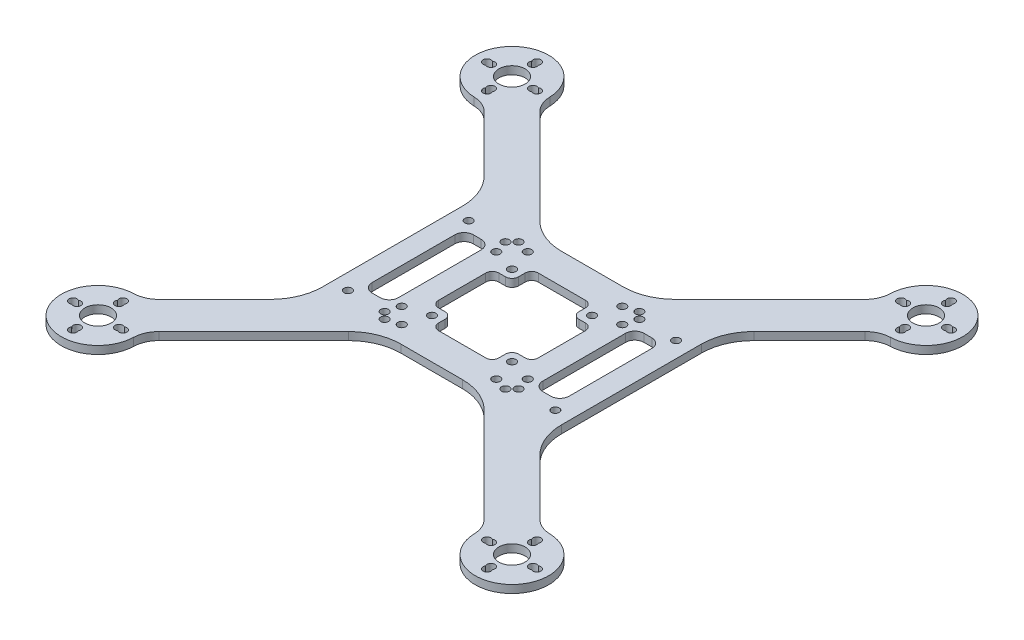
SolidWorks part; units mm, degrees
material "碳纤维板"
ref_plane "前视基准面" through (0, 0, 0) normal (0, 0, 1) x (1, 0, 0)
ref_plane "上视基准面" through (0, 0, 0) normal (0, 1, 0) x (1, 0, 0)
ref_plane "右视基准面" through (0, 0, 0) normal (1, 0, 0) x (0, 0, -1)
sketch "草图1" plane through (0, 0, 0) normal (0, 1, 0) x (1, 0, 0)
  line L1 (-42.5, 30.6) -> (42.5, 30.6)
  line L2 (-45.5, 27.6) -> (-45.5, -27.6)
  line L3 (-42.5, -30.6) -> (42.5, -30.6)
  line L4 (45.5, 27.6) -> (45.5, -27.6)
  line L5 (-45.5, 30.6) -> (45.5, -30.6) construction
  line L6 (-45.5, -30.6) -> (45.5, 30.6) construction
  line L7 (-25.5, 23) -> (25.5, 23) construction
  line L8 (-25.5, 23) -> (-25.5, -23) construction
  line L9 (-25.5, -23) -> (25.5, -23) construction
  line L10 (25.5, 23) -> (25.5, -23) construction
  line L11 (-25.5, 23) -> (25.5, -23) construction
  line L12 (-25.5, -23) -> (25.5, 23) construction
  line L13 (-39.5, -23) -> (39.5, -23) construction
  line L14 (-39.5, -23) -> (-39.5, 23) construction
  line L15 (-39.5, 23) -> (39.5, 23) construction
  line L16 (39.5, -23) -> (39.5, 23) construction
  line L17 (-39.5, -23) -> (39.5, 23) construction
  line L18 (-39.5, 23) -> (39.5, -23) construction
  line L19 (-24, -18) -> (24, -18) construction
  line L20 (-24, -18) -> (-24, 18) construction
  line L21 (-24, 18) -> (24, 18) construction
  line L22 (24, -18) -> (24, 18) construction
  line L23 (-24, -18) -> (24, 18) construction
  line L24 (-24, 18) -> (24, -18) construction
  line L25 (-18, -24) -> (18, -24) construction
  line L26 (-18, -24) -> (-18, 24) construction
  line L27 (-18, 24) -> (18, 24) construction
  line L28 (18, -24) -> (18, 24) construction
  line L29 (-18, -24) -> (18, 24) construction
  line L30 (-18, 24) -> (18, -24) construction
  line L31 (-23, -25.5) -> (23, -25.5) construction
  line L32 (-23, -25.5) -> (-23, 25.5) construction
  line L33 (-23, 25.5) -> (23, 25.5) construction
  line L34 (23, -25.5) -> (23, 25.5) construction
  line L35 (-23, -25.5) -> (23, 25.5) construction
  line L36 (-23, 25.5) -> (23, -25.5) construction
  circle A0 centre (-39.5, 23) radius 1.5
  circle A1 centre (-25.5, 23) radius 1.5
  circle A2 centre (25.5, 23) radius 1.5
  circle A3 centre (39.5, 23) radius 1.5
  circle A4 centre (-39.5, -23) radius 1.5
  circle A5 centre (-25.5, -23) radius 1.5
  circle A6 centre (25.5, -23) radius 1.5
  circle A7 centre (39.5, -23) radius 1.5
  arc A8 (-45.5, -27.6) -> (-42.5, -30.6) centre (-42.5, -27.6) ccw
  arc A9 (42.5, -30.6) -> (45.5, -27.6) centre (42.5, -27.6) ccw
  arc A10 (42.5, 30.6) -> (45.5, 27.6) centre (42.5, 27.6) cw
  arc A11 (-42.5, 30.6) -> (-45.5, 27.6) centre (-42.5, 27.6) ccw
  circle A12 centre (-18, 24) radius 1.5
  circle A13 centre (18, 24) radius 1.5
  circle A14 centre (-18, -24) radius 1.5
  circle A15 centre (18, -24) radius 1.5
  circle A16 centre (24, -18) radius 1.5
  circle A17 centre (24, 18) radius 1.5
  circle A18 centre (-24, 18) radius 1.5
  circle A19 centre (-24, -18) radius 1.5
  circle A20 centre (-23, 25.5) radius 1.5
  circle A21 centre (-23, -25.5) radius 1.5
  circle A22 centre (23, 25.5) radius 1.5
  circle A23 centre (23, -25.5) radius 1.5
  point P0 (0, 0)
  point P6 (0, 0)
  point P11 (0, 0)
  point P42 (0, 0)
  point P47 (0, 0)
  point P60 (0, 0)
  dimension "D5" = 3
  dimension "D4" = 3
  dimension "D13" = 3
  dimension "D16" = 3
  dimension "D1" = 61.2
  dimension "91" = 91
  dimension "D2" = 25.5
  dimension "D3" = 46
  dimension "D7" = 2
  dimension "D8" = 39.5
  dimension "D9" = 48
  dimension "D10" = 36
  dimension "D11" = 36
  dimension "D12" = 48
  dimension "D14" = 46
  dimension "D15" = 51
  dimension "D6" = 2
extrude "凸台-拉伸1" add sketch "草图1" along normal blind 3
sketch "草图2" plane through (0, 3, 0) normal (0, 1, 0) x (1, 0, 0)
  line L0 (-111.5, 0) -> (111.5, 0) construction
  line L1 (-78.8424, 78.8424) -> (78.8424, -78.8424) construction
  line L2 (78.8424, 78.8424) -> (-78.8424, -78.8424) construction
  line L3 (-92.8424, 78.8424) -> (-64.8424, 78.8424) construction
  line L4 (-155.0424, 155.0424) -> (155.0424, 155.0424) construction
  line L5 (-155.0424, 155.0424) -> (-155.0424, -155.0424) construction
  line L6 (-155.0424, -155.0424) -> (155.0424, -155.0424) construction
  line L7 (155.0424, 155.0424) -> (155.0424, -155.0424) construction
  line L8 (-155.0424, 155.0424) -> (155.0424, -155.0424) construction
  line L9 (-155.0424, -155.0424) -> (155.0424, 155.0424) construction
  line L10 (-78.8424, 92.8424) -> (-78.8424, 64.8424) construction
  line L14 (42.5, 30.6) -> (-42.5, 30.6) construction
  line L17 (-61.9255, 72.5321) -> (-19.9934, 30.6)
  line L18 (-72.5321, 61.9255) -> (-51.3579, 40.7513)
  line L21 (-45.5, 23.4123) -> (-45.5, 26.6091)
  line L22 (-45.5, 23.4123) -> (-19.9934, 30.6)
  line L23 (-45.5, 27.6) -> (-45.5, -27.6) construction
  circle A0 centre (0, 0) radius 111.5 construction
  circle A1 centre (-78.8424, 78.8424) radius 76.2 construction
  circle A2 centre (78.8424, 78.8424) radius 76.2 construction
  circle A3 centre (78.8424, -78.8424) radius 76.2 construction
  circle A4 centre (-78.8424, -78.8424) radius 76.2 construction
  arc A5 (-64.8494, 79.2862) -> (-79.2862, 64.8494) centre (-78.8424, 78.8424) ccw
  circle A6 centre (-78.8424, 78.8424) radius 9.5 construction
  circle A7 centre (-78.8424, 88.3424) radius 1.5
  circle A8 centre (-69.3424, 78.8424) radius 1.5
  circle A9 centre (-78.8424, 69.3424) radius 1.5
  circle A10 centre (-88.3424, 78.8424) radius 1.5
  arc A11 (-51.3579, 40.7513) -> (-45.5, 26.6091) centre (-65.5, 26.6091) cw
  arc A12 (-72.5321, 61.9255) -> (-79.2862, 64.8494) centre (-79.6032, 54.8545) ccw
  arc A13 (-61.9255, 72.5321) -> (-64.8494, 79.2862) centre (-54.8545, 79.6032) cw
  circle A16 centre (-78.8424, 78.8424) radius 5
  dimension "D1" = 223
  dimension "D2" = 45
  dimension "D3" = 152.4
  dimension "D5" = 28
  dimension "D6" = 19
  dimension "D7" = 3
  dimension "D10" = 20
  dimension "D12" = 10
  dimension "D13" = 10
  dimension "D14" = 10
  dimension "D9" = 7.5
  dimension "D11" = 26.5
  dimension "D4" = 4
  dimension "D8" = 4
extrude "凸台-拉伸2" add sketch "草图2" against normal up to surface (3 mm away) up to face at (0, 0, 0)
mirror "镜向4" about plane through (0, 0, 0) normal (0, 0, 1) of "凸台-拉伸2"
mirror "镜向5" about plane through (0, 0, 0) normal (1, 0, 0) of "镜向4", "凸台-拉伸2"
fillet "圆角4" radius 20 4 edges at (19.9934, 1.5, 30.6) (-19.9934, 1.5, 30.6) (19.9934, 1.5, -30.6) (-19.9934, 1.5, -30.6)
sketch "草图3" plane through (0, 3, 0) normal (0, 1, 0) x (1, 0, 0)
  line L0 (0, 22.5) -> (-22.5, 0) construction
  line L1 (-27.5, -19.25) -> (27.5, -19.25) construction
  line L2 (-27.5, -19.25) -> (-27.5, 19.25) construction
  line L3 (-27.5, 19.25) -> (27.5, 19.25) construction
  line L4 (27.5, -19.25) -> (27.5, 19.25) construction
  line L5 (-27.5, -19.25) -> (27.5, 19.25) construction
  line L6 (-27.5, 19.25) -> (27.5, -19.25) construction
  line L7 (-11.5, 19) -> (11.5, 19)
  line L8 (-19, 11.5) -> (-19, -11.5)
  line L9 (-11.5, -19) -> (11.5, -19)
  line L10 (19, 11.5) -> (19, -11.5)
  line L11 (-16.3107, 16.3107) -> (16.3107, -16.3107) construction
  line L12 (-16.3107, -16.3107) -> (16.3107, 16.3107) construction
  line L13 (27.5, 19.25) -> (37.5, 19.25)
  line L14 (27.5, 19.25) -> (27.5, -19.25)
  line L15 (27.5, -19.25) -> (37.5, -19.25)
  line L16 (37.5, 19.25) -> (37.5, -19.25)
  line L17 (-27.5, 19.25) -> (-37.5, 19.25)
  line L18 (-27.5, 19.25) -> (-27.5, -19.25)
  line L19 (-27.5, -19.25) -> (-37.5, -19.25)
  line L20 (-37.5, 19.25) -> (-37.5, -19.25)
  line L21 (-15.25, 15.25) -> (15.25, 15.25) construction
  line L22 (-15.25, 15.25) -> (-15.25, -15.25) construction
  line L23 (-15.25, -15.25) -> (15.25, -15.25) construction
  line L24 (15.25, 15.25) -> (15.25, -15.25) construction
  line L25 (-15.25, 15.25) -> (15.25, -15.25) construction
  line L26 (-15.25, -15.25) -> (15.25, 15.25) construction
  line L27 (0, 22.5) -> (22.5, 0) construction
  line L28 (-22.5, 0) -> (0, -22.5) construction
  line L29 (22.5, 0) -> (0, -22.5) construction
  line L30 (0, 22.5) -> (0, -22.5) construction
  line L32 (11.5, 11.5) -> (19, 11.5)
  line L33 (11.5, 11.5) -> (11.5, 19)
  line L36 (11.5, 11.5) -> (16.3107, 16.3107) construction
  line L37 (11.5, 19) -> (19, 11.5) construction
  line L38 (-11.5, 11.5) -> (-19, 11.5)
  line L39 (-11.5, 11.5) -> (-11.5, 19)
  line L42 (-11.5, 11.5) -> (-16.3107, 16.3107) construction
  line L43 (-11.5, 19) -> (-19, 11.5) construction
  line L44 (-11.5, -11.5) -> (-19, -11.5)
  line L45 (-11.5, -11.5) -> (-11.5, -19)
  line L48 (-11.5, -11.5) -> (-16.3107, -16.3107) construction
  line L49 (-11.5, -19) -> (-19, -11.5) construction
  line L50 (11.5, -11.5) -> (19, -11.5)
  line L51 (11.5, -11.5) -> (11.5, -19)
  line L54 (11.5, -11.5) -> (16.3107, -16.3107) construction
  line L55 (11.5, -19) -> (19, -11.5) construction
  circle A0 centre (-25.5, 23) radius 2.4 construction
  circle A1 centre (-25.5, 23) radius 1.5 construction
  circle A2 centre (15.25, 15.25) radius 1.5
  circle A3 centre (15.25, -15.25) radius 1.5
  circle A4 centre (-15.25, 15.25) radius 1.5
  circle A5 centre (-15.25, -15.25) radius 1.5
  point P0 (0, 0)
  point P11 (0, 0)
  point P20 (0, 0)
  point P29 (0, 0)
  dimension "D2" = 4.8
  dimension "D6" = 3
  dimension "D1" = 55
  dimension "38.5" = 38.5
  dimension "D3" = 10
  dimension "D4" = 19
  dimension "D5" = 30.5
  dimension "D7" = 19
  dimension "D8" = 45
extrude "切除-拉伸1" cut sketch "草图3" against normal through all
fillet "圆角6" radius 3.5 8 edges at (27.5, 1.5, -19.25) (37.5, 1.5, -19.25) (27.5, 1.5, 19.25) (37.5, 1.5, 19.25) (-27.5, 1.5, 19.25) (-37.5, 1.5, 19.25) (-27.5, 1.5, -19.25) (-37.5, 1.5, -19.25)
fillet "圆角7" radius 2.5 12 edges at (-19, 1.5, 11.5) (-11.5, 1.5, 11.5) (-11.5, 1.5, 19) (11.5, 1.5, 19) (11.5, 1.5, 11.5) (19, 1.5, 11.5) (19, 1.5, -11.5) (11.5, 1.5, -11.5) (11.5, 1.5, -19) (-19, 1.5, -11.5) (-11.5, 1.5, -11.5) (-11.5, 1.5, -19)
sketch "草图4" plane through (0, 3, 0) normal (0, 1, 0) x (1, 0, 0)
  line L0 (-78.8424, 78.8424) -> (-70.8424, 78.8424) construction
  circle A0 centre (-78.8424, 78.8424) radius 8 construction
  circle A1 centre (-70.8424, 78.8424) radius 1.5
  circle A2 centre (-78.8424, 70.8424) radius 1.5
  circle A3 centre (-86.8424, 78.8424) radius 1.5
  circle A4 centre (-78.8424, 86.8424) radius 1.5
  point P5 (0, 0)
  point P6 (0, 0)
  dimension "D1" = 16
  dimension "D2" = 3
  dimension "D3" = 4
extrude "切除-拉伸2" cut sketch "草图4" against normal through all
ref_axis "基准轴1" through (0, 0, 0) along (0, 1, 0)
pattern_circular "阵列(圆周)1" count 4 over 360 about axis through (0, 0, 0) along (0, 1, 0) of "切除-拉伸2"
